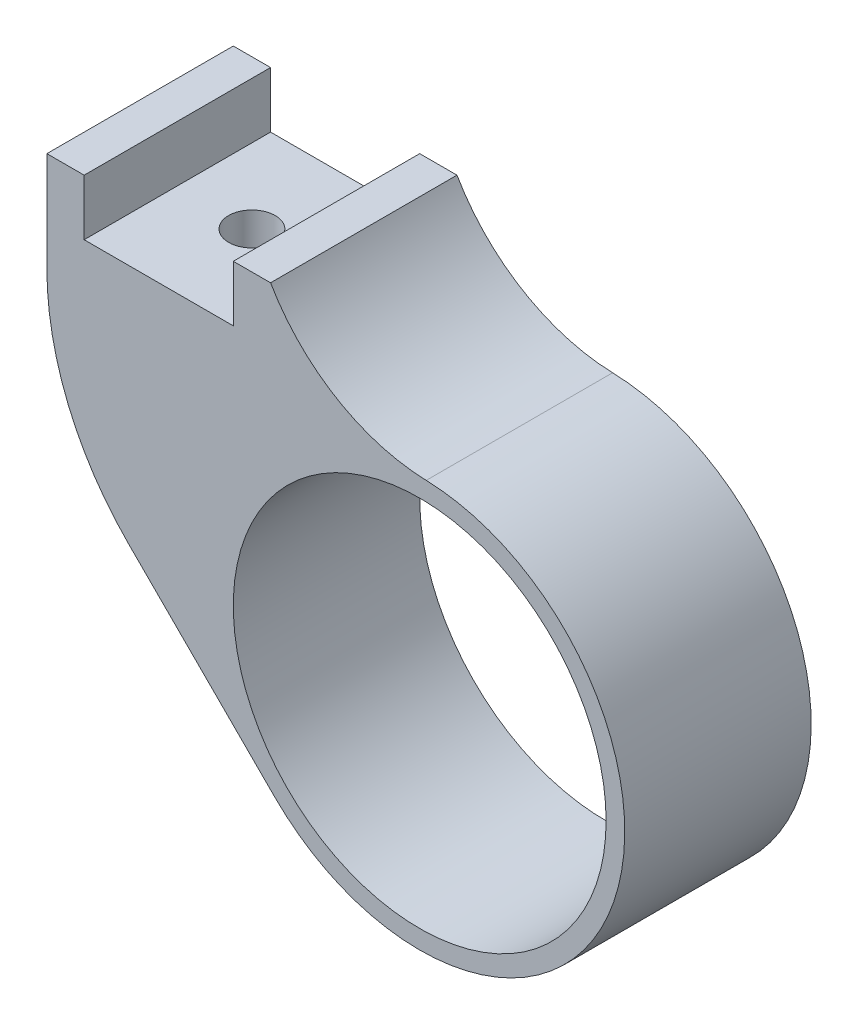
SolidWorks part; units mm, degrees
material "Thornel VCB-20 Carbon Cloth"
ref_plane "Спереди" through (0, 0, 0) normal (0, 0, 1) x (1, 0, 0)
ref_plane "Сверху" through (0, 0, 0) normal (0, 1, 0) x (1, 0, 0)
ref_plane "Справа" through (0, 0, 0) normal (1, 0, 0) x (0, 0, -1)
other "Configuration Table"
sketch "Sketch1" plane through (0, 0, 0) normal (0, 0, 1) x (1, 0, 0)
  line L0 (-20, 16) -> (-20, 4.4437)
  line L1 (-10, 16) -> (-8, 16)
  line L2 (-10, 16) -> (-10, 13)
  line L4 (-8, 16) -> (-8, 7.5498)
  line L5 (-20, 16) -> (-18, 16)
  line L8 (-18, 16) -> (-18, 13)
  line L9 (-10, 13) -> (-18, 13)
  line L11 (-7.7782, -7.7782) -> (-20, 4.4437)
  circle A0 centre (0, 0) radius 10
  circle A1 centre (0, 0) radius 11
  point P12 (-9.2775, 5.91)
  point P14 (-20, 1.4534)
  point P15 (-15.0574, 2.1422)
  point P17 (-14, 13)
  dimension "inner_diameter" = 20
  dimension "D2" = 22
  dimension "D3" = 3
  dimension "D4" = 2
  dimension "D5" = 8
  dimension "D6" = 2
  dimension "D7" = 13
  dimension "D1" = 14
  dimension "D8" = 135
extrude "Boss-Extrude1" add sketch "Sketch1" along normal blind 10 contours A1 L4 L1 L2 L9 L8 L5 L0 | A1 A0 region at (-14.0319, 7.0814, 0) region at (-10.6878, -0.1547, 0)
fillet "Fillet1" radius 10 1 edges at (-8, 7.5498, 5)
hole_wizard "M3 Tapped Hole1" positions "Sketch2" profile "Sketch3" tap size "M3" standard "ISO" end condition up to next
sketch "Sketch2" plane through (0, 13, 0) normal (0, 1, 0) x (1, 0, 0)
  line L0 (-18, -10) -> (-10, 0)
  line L2 (-18, 0) -> (-10, -10)
  point P0 (-14, -5)
  point P13 (-9, -5)
  point P14 (-10, 0)
cosmetic thread "Hole Thread1" parameters "D1"=4, "D2"=3
sketch "Sketch3" plane through (-14, 13, 5) normal (1, 0, 0) x (0, 0, 1)
  line L0 (0, 0) -> (0, 14.5563)
  line L1 (0, 14.5563) -> (1.25, 14.5563)
  line L2 (1.25, 14.5563) -> (1.25, 0)
  line L5 (1.25, 0) -> (0, 0)
  line L11 (0, -6.35) -> (0, 107.95) construction
  dimension "Thru Tap Drill Dia." = 2.5
  dimension "Thru Tap Drill Depth" = 14.5563
ref_plane "Plane1" through (0, 3, 0) normal (0, 1, 0) x (1, 0, 0)
sketch "Sketch4" plane through (0, 3, 0) normal (0, 1, 0) x (1, 0, 0)
  circle A0 centre (-14, -5) radius 1.25 construction
  circle A1 centre (-14, -5) radius 1.25
  circle A2 centre (-14, -5) radius 2.75
  dimension "D1" = 5.5
fillet "Fillet2" radius 15 1 edges at (-20, 4.4437, 5)
equation "\"inner_diameter\"=20"
equation "\"inner_diameter@Sketch1\" = \"inner_diameter\""
equation "\"D7@Sketch1\"=\"inner_diameter\"/2+3"
equation "\"D2@Sketch1\"=\"inner_diameter\"+2"
